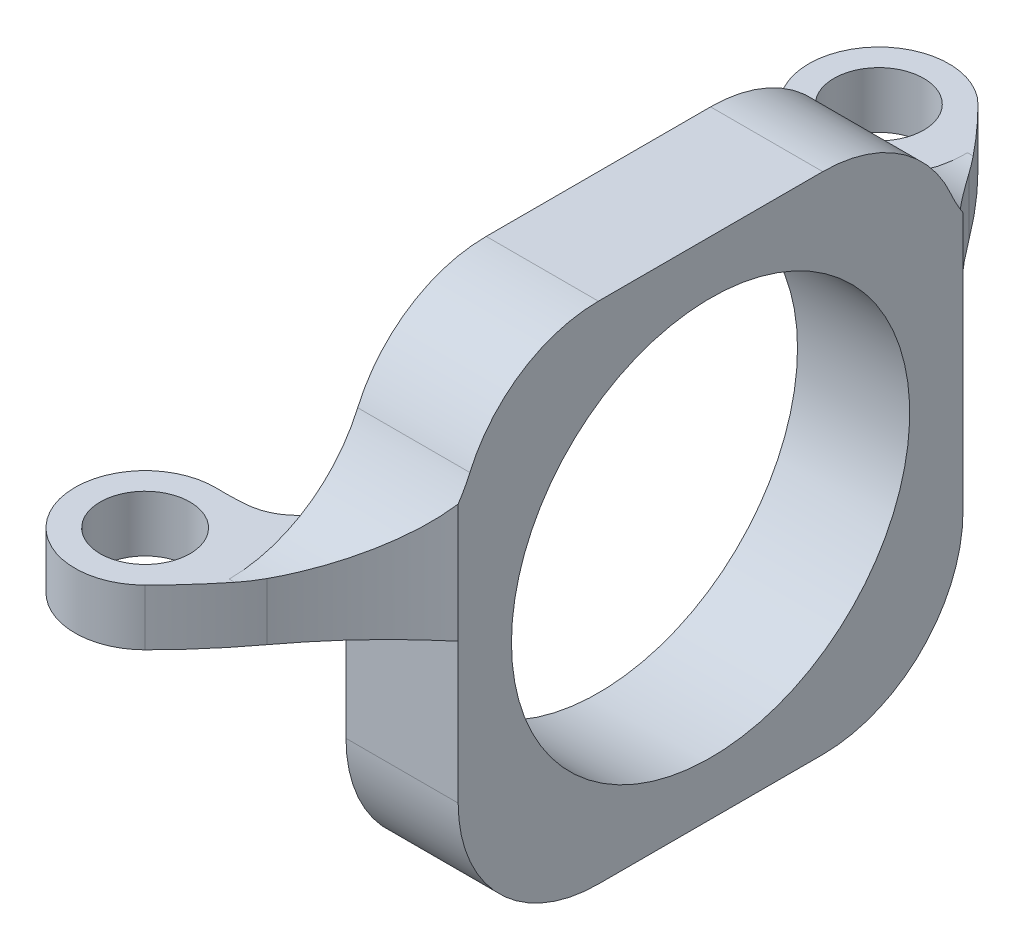
SolidWorks part; units mm, degrees
ref_plane "Front Plane" through (0, 0, 0) normal (0, 0, 1) x (1, 0, 0)
ref_plane "Top Plane" through (0, 0, 0) normal (0, 1, 0) x (1, 0, 0)
ref_plane "Right Plane" through (0, 0, 0) normal (1, 0, 0) x (0, 0, -1)
sketch "Sketch1" plane through (0, 0, 0) normal (0, 1, 0) x (1, 0, 0)
  line L0 (0, 0) -> (14.8492, -14.8492) construction
  line L1 (-13.0815, -13.0815) -> (13.0815, -13.0815) construction
  line L2 (-13.0815, -13.0815) -> (-13.0815, 13.0815) construction
  line L3 (-13.0815, 13.0815) -> (13.0815, 13.0815) construction
  line L4 (13.0815, -13.0815) -> (13.0815, 13.0815) construction
  line L5 (-13.0815, -13.0815) -> (13.0815, 13.0815) construction
  line L6 (-13.0815, 13.0815) -> (13.0815, -13.0815) construction
  line L7 (0, 0) -> (14.8492, 14.8492) construction
  line L8 (0, 0) -> (21, 0) construction
  line L9 (18.9737, -9) -> (20.1632, -9)
  line L10 (20.1632, -9) -> (16.1632, -9) construction
  line L11 (20.1632, -9) -> (20.1632, 9) construction
  line L12 (20.1632, 9) -> (16.1632, 9) construction
  line L13 (16.1632, -9) -> (16.1632, 9) construction
  line L14 (20.1632, -9) -> (16.1632, 9) construction
  line L15 (20.1632, 9) -> (16.1632, -9) construction
  line L16 (20.1632, -9) -> (20.1632, -5.8689)
  line L17 (18.9737, 9) -> (20.1632, 9)
  line L18 (20.1632, 9) -> (20.1632, 5.8689)
  line L19 (16.1632, 9) -> (16.1632, -9)
  circle A0 centre (0, 0) radius 18.5 construction
  circle A1 centre (0, 0) radius 15.5 construction
  circle A2 centre (13.0815, 13.0815) radius 1.6
  circle A3 centre (13.0815, -13.0815) radius 1.6
  circle A5 centre (13.0815, 13.0815) radius 2.5 construction
  circle A6 centre (13.0815, -13.0815) radius 2.5 construction
  circle A7 centre (0, 0) radius 21 construction
  arc A8 (14.7258, 11.1983) -> (14.7258, -11.1983) centre (0, 0) cw construction
  arc A9 (14.7258, 11.1983) -> (14.8492, 14.8492) centre (13.0815, 13.0815) cw
  arc A10 (14.7258, -11.1983) -> (14.8492, -14.8492) centre (13.0815, -13.0815) ccw
  arc A11 (14.7258, 11.1983) -> (16.1632, 9) centre (0, 0) cw
  arc A12 (16.1632, -9) -> (14.7258, -11.1983) centre (0, 0) cw
  arc A13 (14.8492, 14.8492) -> (18.9737, 9) centre (0, 0) cw
  arc A14 (14.8492, -14.8492) -> (18.9737, -9) centre (0, 0) ccw
  arc A15 (20.1632, 5.8689) -> (20.1632, -5.8689) centre (0, 0) cw
  point P18 (14.8492, 14.8492)
  point P19 (14.8492, -14.8492)
  point P20 (20.1632, -5.8689)
  point P21 (18.1632, 0)
  point P32 (20.1632, 5.8689)
  dimension "D1" = 31
  dimension "D2" = 37
  dimension "D3" = 3.2
  dimension "D4" = 3.2
  dimension "D5" = 5
  dimension "D6" = 5
  dimension "D7" = 18
  dimension "D8" = 4
extrude "Boss-Extrude1" add sketch "Sketch1" along normal blind 2 contours A15 L18 L17 A13 A9 A11 L19 A12 A10 A14 L9 L16 A3 A2 region at (17.0696, 0, 0)
sketch "Sketch2" plane through (0, 2, 0) normal (0, 1, 0) x (1, 0, 0)
  line L1 (20.1632, 9) -> (16.1632, 9)
  line L2 (20.1632, 9) -> (20.1632, -9)
  line L3 (20.1632, -9) -> (16.1632, -9)
  line L4 (16.1632, 9) -> (16.1632, -9)
extrude "Boss-Extrude2" add sketch "Sketch2" along normal blind 6 and the other way blind 12
sketch "Sketch3" plane through (20.1632, 0, 0) normal (1, 0, 0) x (0, 0, -1)
  line L0 (-5.8689, 0) -> (5.8689, 0) construction
  circle A0 centre (0, -1) radius 7.1
  dimension "D2" = 14.2
  dimension "D1" = 1
extrude "Cut-Extrude1" cut sketch "Sketch3" against normal blind 5 and the other way blind 5
fillet "Fillet1" radius 5 4 edges at (18.1632, -10, -9) (18.1632, -10, 9) (18.1632, 8, -9) (18.1632, 8, 9)
fillet "Fillet2" radius 21 2 edges at (18.9737, 1, -9) (18.9737, 1, 9)
fillet "Fillet4" radius 5 2 edges at (16.1632, 1, 9) (16.1632, 1, -9)
fillet "Fillet5" radius 10 2 edges at (14.7258, 1, 11.1983) (14.7258, 1, -11.1983)
fillet "Fillet6" radius 2 2 edges at (15.2978, 1, 10.4033) (15.2978, 1, -10.4033)
fillet "Fillet7" radius 5 2 edges at (18.1632, 2, -9) (18.1632, 2, 9)
